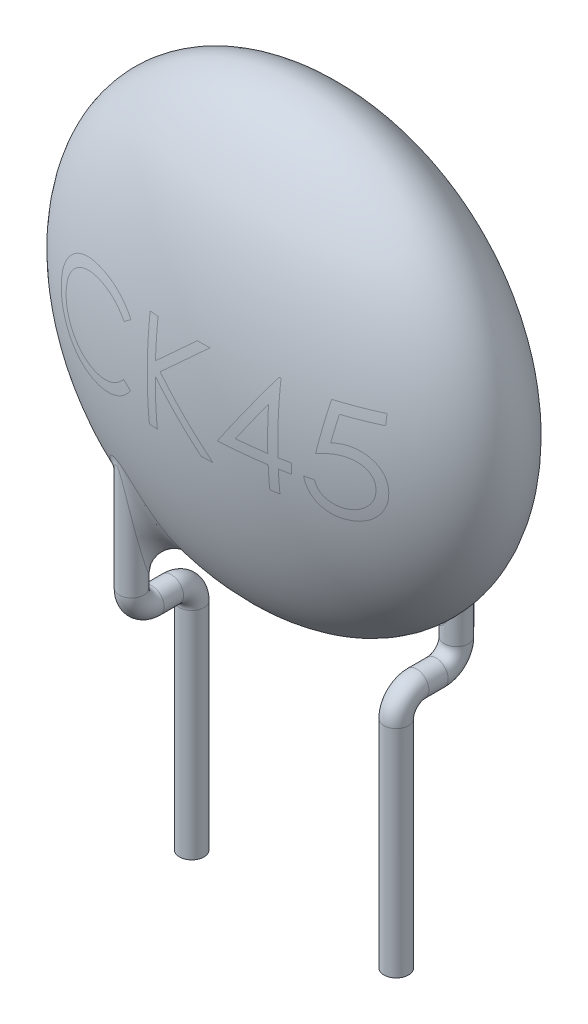
SolidWorks part; units mm, degrees
ref_plane "Front Plane" through (0, 0, 0) normal (0, 0, 1) x (1, 0, 0)
ref_plane "Top Plane" through (0, 0, 0) normal (0, 1, 0) x (1, 0, 0)
ref_plane "Right Plane" through (0, 0, 0) normal (1, 0, 0) x (0, 0, -1)
sketch "Sketch1" plane through (0, 0, 0) normal (0, 1, 0) x (1, 0, 0)
  line L0 (0, 0) -> (0, 2.9713) construction
  circle A0 centre (-2.5, 0) radius 0.3
  circle A1 centre (2.5, 0) radius 0.3
  dimension "D3" = 0.6
  dimension "D1" = 2.5
extrude "Boss-Extrude1" add sketch "Sketch1" against normal blind 5
sketch "Sketch4" plane through (0, 0, 0) normal (0, 1, 0) x (1, 0, 0)
  circle A1 centre (2.5, 0) radius 0.3
  circle A2 centre (2.5, 0) radius 0.3
  dimension "D1" = 0
sketch "Sketch2" plane through (0, 0, 0) normal (1, 0, 0) x (0, 0, -1)
  line L0 (0, 7) -> (7.789, 7) construction
  line L1 (0, 1.5) -> (2.5, 1.5) construction
  line L2 (0, 1.5) -> (0, 12.5) construction
  line L3 (0, 12.5) -> (2.5, 12.5) construction
  line L4 (2.5, 1.5) -> (2.5, 12.5) construction
  line L5 (0, 1.5) -> (0, 7)
  line L6 (0, 7) -> (2.5, 7)
  ellipse E0 centre (0, 7) end of major axis (0, 12.5) minor radius 2.5 (2.5, 7) -> (0, 1.5) cw
  dimension "D1" = 11
  dimension "D2" = 2.5
  dimension "D3" = 7
revolve "Revolve1" add sketch "Sketch2" angle 360 about L0
mirror "Mirror2" about plane through (0, 0, 0) normal (0, 0, 1) of bodies 103
ref_plane "Plane1" through (-2.5, 0, 0) normal (1, 0, 0) x (0, 0, -1)
sketch "Sketch5" plane through (-2.5, 0, 0) normal (1, 0, 0) x (0, 0, -1)
  line L0 (0, 0) -> (0, 0.2803)
  line L1 (-0.5, 0.7803) -> (-0.9714, 0.7803)
  line L2 (-1.4714, 1.2803) -> (-1.4714, 4.8497)
  arc A0 (-0.9714, 0.7803) -> (-1.4714, 1.2803) centre (-0.9714, 1.2803) cw
  arc A1 (0, 0.2803) -> (-0.5, 0.7803) centre (-0.5, 0.2803) ccw
  dimension "D1" = 0.5
sketch "Sketch6" plane through (0, 0, 0) normal (0, 1, 0) x (1, 0, 0)
  circle A1 centre (-2.5, 0) radius 0.3
  circle A2 centre (-2.5, 0) radius 0.3
  dimension "D1" = 0
sweep "Sweep1" add profiles "Sketch6" path "Sketch5"
fillet "Fillet1" radius 0.5 1 edges at (-2.6436, 2.9753, 1.208)
ref_plane "Plane2" through (2.5, 0, 0) normal (1, 0, 0) x (0, 0, -1)
sketch "Sketch7" plane through (2.5, 0, 0) normal (1, 0, 0) x (0, 0, -1)
  line L6 (0, 0) -> (0, 2.9515) construction
  line L7 (0, 0) -> (0, 0.2803)
  line L8 (0.5, 0.7803) -> (0.9714, 0.7803)
  line L9 (1.4714, 1.2803) -> (1.4714, 4.8497)
  arc A0 (0, 0.2803) -> (-0.5, 0.7803) centre (-0.5, 0.2803) ccw construction
  arc A4 (0, 0.2803) -> (0.5, 0.7803) centre (0.5, 0.2803) cw
  arc A5 (1.4714, 1.2803) -> (0.9714, 0.7803) centre (0.9714, 1.2803) cw
sketch "Sketch8" plane through (0, 0, 0) normal (0, 1, 0) x (1, 0, 0)
  circle A1 centre (2.5, 0) radius 0.3
  circle A2 centre (2.5, 0) radius 0.3
  dimension "D1" = 0
sweep "Sweep2" add profiles "Sketch8" path "Sketch7"
fillet "Fillet2" radius 0.5 1 edges at (2.5092, 4.0388, -1.7713)
sketch "Sketch9" plane through (0, 0, 0) normal (0, 0, 1) x (1, 0, 0)
  text T0 "CK45" font "Century Gothic" height in points 9
split line "Split Line1"
